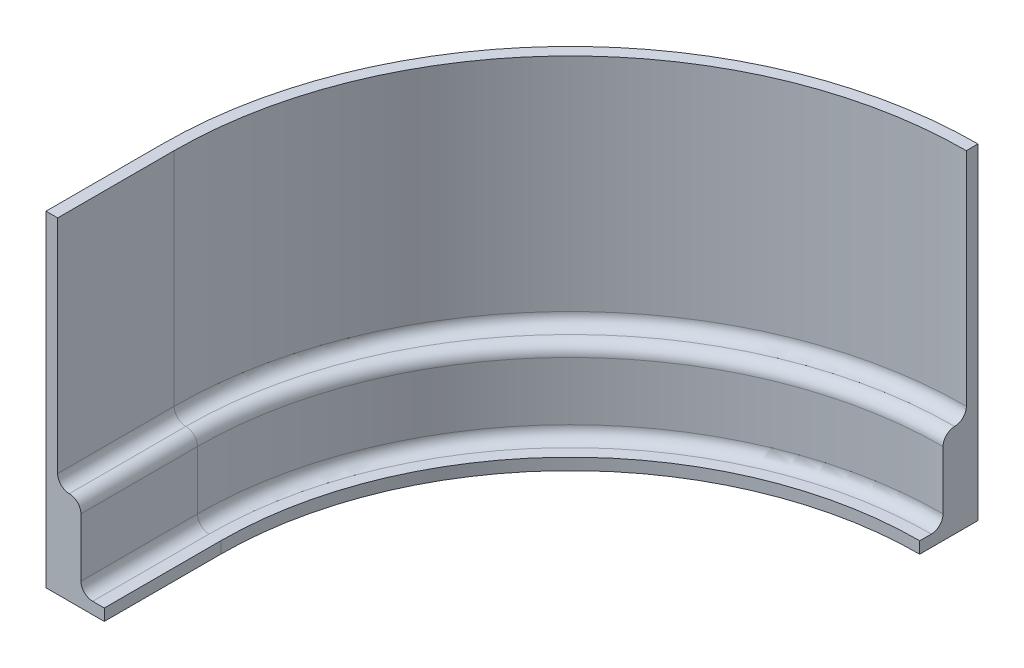
SolidWorks part; units mm, degrees
material "AISI 4340 Steel, annealed"
ref_plane "Front Plane" through (0, 0, 0) normal (0, 0, 1) x (1, 0, 0)
ref_plane "Top Plane" through (0, 0, 0) normal (0, 1, 0) x (1, 0, 0)
ref_plane "Right Plane" through (0, 0, 0) normal (1, 0, 0) x (0, 0, -1)
sketch "Sketch1" plane through (0, 0, 0) normal (0, 1, 0) x (1, 0, 0)
  line L0 (0, 0) -> (-25, 0) construction
  line L4 (150, 150) -> (150, 175)
  line L5 (-25, 0) -> (-25, -50)
  line L6 (-25, -50) -> (0, -50)
  line L7 (0, -50) -> (0, 0)
  arc A0 (0, 0) -> (150, 150) centre (150, 0) cw
  arc A1 (-25, 0) -> (150, 175) centre (150, 0) cw
  dimension "D1" = 150
  dimension "D2" = 25
  dimension "D3" = 50
extrude "Bottom level" add sketch "Sketch1" along normal blind 5
sketch "Sketch2" plane through (0, 5, 0) normal (0, 1, 0) x (1, 0, 0)
  line L7 (-25, 0) -> (-25, -50) construction
  line L8 (-25, 0) -> (-25, -50)
  line L9 (-10, 0) -> (-10, -50)
  line L10 (-25, -50) -> (-10, -50)
  line L11 (150, 160) -> (150, 175)
  arc A3 (150, 175) -> (-25, 0) centre (150, 0) ccw construction
  arc A4 (150, 175) -> (-25, 0) centre (150, 0) ccw
  arc A5 (150, 160) -> (-10, 0) centre (150, 0) ccw
  dimension "D1" = 15
extrude "Mid level" add sketch "Sketch2" along normal blind 35
sketch "Sketch3" plane through (0, 40, 0) normal (0, 1, 0) x (1, 0, 0)
  line L5 (-25, 0) -> (-25, -50) construction
  line L6 (-25, 0) -> (-25, -50)
  line L7 (-20, 0) -> (-20, -50)
  line L8 (150, 170) -> (150, 175)
  line L9 (-25, -50) -> (-20, -50)
  arc A3 (150, 175) -> (-25, 0) centre (150, 0) ccw construction
  arc A4 (150, 175) -> (-25, 0) centre (150, 0) ccw
  arc A5 (150, 170) -> (-20, 0) centre (150, 0) ccw
  dimension "D1" = 5
extrude "Guard rail" add sketch "Sketch3" along normal blind 100
fillet "Rounding" radius 5 6 edges at (-10, 5, 25) (-10, 40, 25) (-20, 40, 25) (36.8629, 5, -113.1371) (36.8629, 40, -113.1371) (29.7918, 40, -120.2082)
